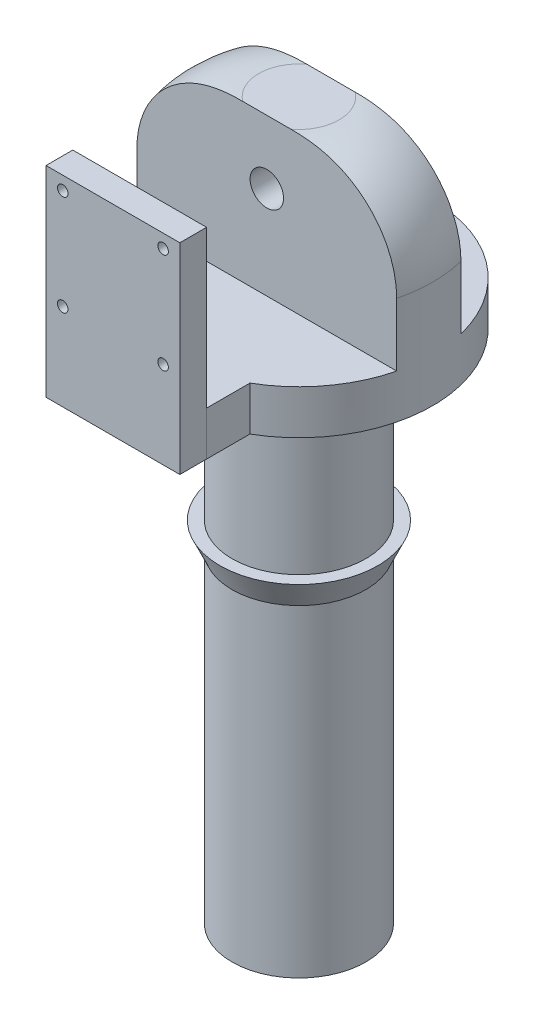
SolidWorks part; units mm, degrees
material "TPU"
ref_plane "Front Plane" through (0, 0, 0) normal (0, 0, 1) x (1, 0, 0)
ref_plane "Top Plane" through (0, 0, 0) normal (0, 1, 0) x (1, 0, 0)
ref_plane "Right Plane" through (0, 0, 0) normal (1, 0, 0) x (0, 0, -1)
sketch "Sketch1" plane through (0, 0, 0) normal (0, 1, 0) x (1, 0, 0)
  circle A0 centre (0, 0) radius 12.7
  dimension "D1" = 25.4
extrude "Part that goes into base" add sketch "Sketch1" along normal blind 97.79
sketch "Sketch2" plane through (0, 0, 0) normal (0, 0, 1) x (1, 0, 0)
  line L0 (12.7, 97.79) -> (-12.7, 97.79) construction
  line L1 (12.7, 97.79) -> (-12.7, 97.79)
  line L2 (12.7, 97.79) -> (12.7, 66.294) construction
  line L3 (12.7, 66.294) -> (14.986, 66.294)
  line L4 (14.986, 66.294) -> (12.7, 61.214)
  line L5 (12.7, 61.214) -> (12.7, 66.294)
  line L6 (0, 97.79) -> (0, 52.1662) construction
  dimension "D1" = 31.496
  dimension "D2" = 2.286
  dimension "D3" = 5.08
revolve "Clip in mechanism" add sketch "Sketch2" angle 360 about L6 region at (13.462, 64.6007, 0)
sketch "Sketch3" plane through (0, 97.79, 0) normal (0, 1, 0) x (1, 0, 0)
  circle A0 centre (0, 0) radius 25.4
  dimension "D1" = 50.8
extrude "Top part Extrude" add sketch "Sketch3" along normal blind 38.1
ref_plane "Plane1" through (50.8, 0, 0) normal (1, 0, 0) x (0, 0, -1)
sketch "Sketch4" plane through (50.8, 0, 0) normal (1, 0, 0) x (0, 0, -1)
  line L0 (25.4, 135.89) -> (-25.4, 135.89) construction
  line L1 (25.4, 135.89) -> (-25.4, 135.89)
  line L2 (-12.7, 97.79) -> (12.7, 97.79) construction
  line L8 (6.096, 135.89) -> (6.096, 106.172)
  line L10 (25.4, 97.79) -> (25.4, 135.89) construction
  line L11 (25.4, 106.172) -> (25.4, 135.89)
  line L12 (6.096, 135.89) -> (25.4, 135.89)
  line L13 (25.4, 106.172) -> (6.096, 106.172)
  line L14 (-25.4, 106.172) -> (-6.096, 106.172)
  line L15 (-25.4, 135.89) -> (-6.096, 135.89)
  line L18 (-6.096, 135.89) -> (-6.096, 106.172)
  line L19 (-25.4, 135.89) -> (-25.4, 106.172)
  dimension "D1" = 8.382
  dimension "D3" = 8.382
  dimension "D4" = 19.304
  dimension "D5" = 8.382
  dimension "D6" = 19.304
extrude "Cut to Accommodate Encoder" cut sketch "Sketch4" against normal through all
sketch "Sketch5" plane through (0, 106.172, 0) normal (0, 1, 0) x (1, 0, 0)
  line L0 (-13.191, -27.686) -> (15.1785, -27.686)
  line L1 (24.6576, -6.096) -> (24.6576, -40.386)
  line L2 (-24.6576, -6.096) -> (24.6576, -6.096) construction
  line L3 (-24.6576, -6.096) -> (-24.6576, -40.386)
  line L4 (-24.6576, -40.386) -> (24.6576, -40.386)
  arc A0 (24.6576, -6.096) -> (-24.6576, -6.096) centre (0, 0) cw
  dimension "D1" = 21.59
  dimension "D2" = 34.29
sketch "Sketch7" plane through (0, 0, -6.096) normal (0, 0, -1) x (-1, 0, 0)
  line L0 (0, 135.89) -> (0, 123.825) construction
  line L1 (24.6576, 135.89) -> (-24.6576, 135.89) construction
  circle A0 centre (0, 123.825) radius 3.175
  dimension "D2" = 6.35
  dimension "D1" = 12.065
extrude "Bolt Hole" cut sketch "Sketch7" against normal up to surface (12.192 mm away) up to face at (0, 121.031, 6.096)
fillet "Fillet to Accommodate shoulder" radius 17.78 2 edges at (-25.4, 135.89, 0) (25.4, 135.89, 0)
ref_plane "Plane2" through (0, 0, 26.416) normal (0, 0, 1) x (1, 0, 0)
sketch "Sketch11" plane through (0, 135.89, 0) normal (0, 1, 0) x (1, 0, 0)
  line L1 (12.7, -30.226) -> (12.7, -35.306)
  line L2 (12.7, -35.306) -> (-12.7, -35.306)
  line L3 (-12.7, -35.306) -> (-12.7, -30.226)
  line L5 (0, 0) -> (0, -31.0003) construction
  line L8 (-8.6658, -30.226) -> (-12.7, -30.226)
  line L9 (8.6658, -30.226) -> (12.7, -30.226)
  line L11 (-8.6658, -30.226) -> (8.6658, -30.226)
  line L12 (4.572, -6.096) -> (24.6576, -6.096) construction
  dimension "D1" = 25.4
  dimension "D2" = 29.21
  dimension "D3" = 24.13
extrude "Boss-Extrude1" add sketch "Sketch11" against normal up to surface (38.1 mm away) up to face at (0, 97.79, 12.7)
sketch "Sketch12" plane through (0, 106.172, 0) normal (0, 1, 0) x (1, 0, 0)
  line L0 (12.7, -23.876) -> (12.7, -21.997)
  line L1 (-12.7, -23.876) -> (-12.7, -21.997)
  line L4 (-12.7, -23.876) -> (-12.7, -30.226)
  line L5 (-12.7, -30.226) -> (12.7, -30.226)
  line L6 (12.7, -30.226) -> (12.7, -23.876)
  arc A0 (-24.6576, -6.096) -> (24.6576, -6.096) centre (0, 0) ccw construction
  arc A1 (-24.6576, -6.096) -> (24.6576, -6.096) centre (0, 0) ccw construction
  arc A2 (-8.6658, -23.876) -> (-12.7, -21.997) centre (0, 0) cw
  arc A3 (12.7, -21.997) -> (8.6658, -23.876) centre (0, 0) cw
  arc A4 (-8.6658, -23.876) -> (8.6658, -23.876) centre (0, 0) ccw
extrude "Boss-Extrude2" add sketch "Sketch12" against normal up to surface (8.382 mm away) up to face at (0, 97.79, 12.7)
sketch "Sketch13" plane through (0, 0, 30.226) normal (0, 0, -1) x (-1, 0, 0)
  line L0 (12.7, 135.89) -> (-12.7, 135.89) construction
  line L1 (0, 135.89) -> (0, 111.6123) construction
  line L2 (-12.7, 123.825) -> (12.3879, 123.825) construction
  line L3 (-12.7, 97.79) -> (-12.7, 135.89) construction
  circle A0 centre (9.525, 133.35) radius 1
  circle A1 centre (-9.525, 133.35) radius 1
  circle A2 centre (-9.525, 114.3) radius 1
  circle A3 centre (9.525, 114.3) radius 1
  circle A4 centre (0, 123.825) radius 3.175 construction
  circle A5 centre (0, 123.825) radius 3.175
  dimension "D1" = 9.525
  dimension "D2" = 9.525
  dimension "D3" = 2.54
  dimension "D4" = 0
extrude "Cut-Extrude1" cut sketch "Sketch13" against normal up to surface (5.08 mm away) contours A2 | A1 | A3 | A0 region at (9.525, 114.3, 30.226) up to face at (0, 116.84, 35.306)
